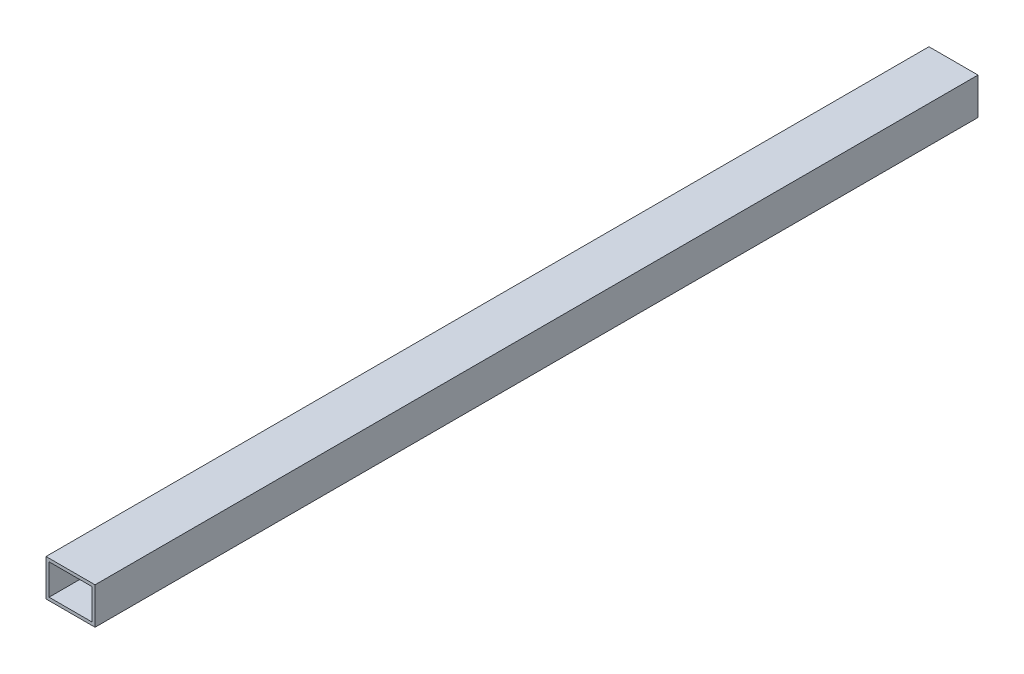
SolidWorks part; units mm, degrees
ref_plane "Front Plane" through (0, 0, 0) normal (0, 0, 1) x (1, 0, 0)
ref_plane "Top Plane" through (0, 0, 0) normal (0, 1, 0) x (1, 0, 0)
ref_plane "Right Plane" through (0, 0, 0) normal (1, 0, 0) x (0, 0, -1)
sketch "Sketch1" plane through (0, 0, 0) normal (0, 0, 1) x (1, 0, 0)
  line L0 (25.4, 0) -> (22.225, 0) construction
  line L1 (-25.4, 0) -> (25.4, 0) construction
  line L2 (0, 19.05) -> (0, -19.05)
  point P7 (0, 0)
sketch "Sketch2" plane through (0, 0, 0) normal (1, 0, 0) x (0, 0, -1)
  line L0 (457.2, 0) -> (-457.2, 0)
  point P4 (0, 0)
  dimension "Length" = 914.4
sketch "Sketch3" plane through (0, 0, 0) normal (0, 0, 1) x (1, 0, 0)
  line L0 (-25.4, 0) -> (25.4, 0) construction
  line L5 (25.4, -19.05) -> (-25.4, -19.05)
  line L6 (25.4, -19.05) -> (25.4, 19.05)
  line L11 (25.4, 19.05) -> (-25.4, 19.05)
  line L12 (-25.4, -19.05) -> (-25.4, 19.05)
  line L14 (25.4, -19.05) -> (-25.4, 19.05) construction
  line L15 (25.4, 19.05) -> (-25.4, -19.05) construction
  line L16 (22.225, -15.875) -> (-22.225, -15.875)
  line L17 (22.225, -15.875) -> (22.225, 15.875)
  line L18 (22.225, 15.875) -> (-22.225, 15.875)
  line L19 (-22.225, -15.875) -> (-22.225, 15.875)
  line L20 (22.225, -15.875) -> (-22.225, 15.875) construction
  line L21 (22.225, 15.875) -> (-22.225, -15.875) construction
  point P0 (0, 0)
  point P5 (0, 0)
  point P13 (22.225, -19.05)
  dimension "D1" = 3.175
  dimension "D4" = 38.1
  dimension "D2" = 3.175
extrude "Boss-Extrude1" add sketch "Sketch3" along normal up to vertex (457.2 mm away) and the other way up to vertex (457.2 mm away) up to point (0, 0, 457.2) other way up to point (0, 0, -457.2)
sketch "Sketch5" plane through (0, 0, 0) normal (1, 0, 0) x (0, 0, -1)
  line L0 (-457.2, 0) -> (457.2, 0) construction
  line L3 (-457.2, -19.05) -> (-457.2, 19.05) construction
  line L4 (457.2, -19.05) -> (457.2, 19.05) construction
  point P6 (-400.05, 0)
  point P7 (-381, 0)
  point P8 (381, 0)
  point P10 (400.05, 0)
  dimension "D1" = 57.15
  dimension "D3" = 57.15
  dimension "D4" = 76.2
sketch "Sketch7" plane through (0, -19.05, 0) normal (0, -1, 0) x (1, 0, 0)
  line L0 (0, 457.2) -> (0, 152.4)
  line L1 (-25.4, 457.2) -> (25.4, 457.2) construction
  point P6 (0, 152.4)
  dimension "D1" = 304.8
equation "\"D1@Sketch3\"=\"Wall thickness@Sketch1\""
equation "\"D1@Sketch5\"=\"Width@Sketch1\"*1.125"
equation "\"D2@Sketch5\"=\"Width@Sketch1\"*1.5"
equation "\"D3@Sketch5\"=\"D1@Sketch5\""
equation "\"D4@Sketch5\"=\"D2@Sketch5\""
equation "\"D2@Sketch3\"=\"Wall Thickness@Sketch1\""
equation "\"actuatorDistanceFromTop\"=12"
equation "\"D1@Sketch7\"=\"actuatorDistanceFromTop\""
